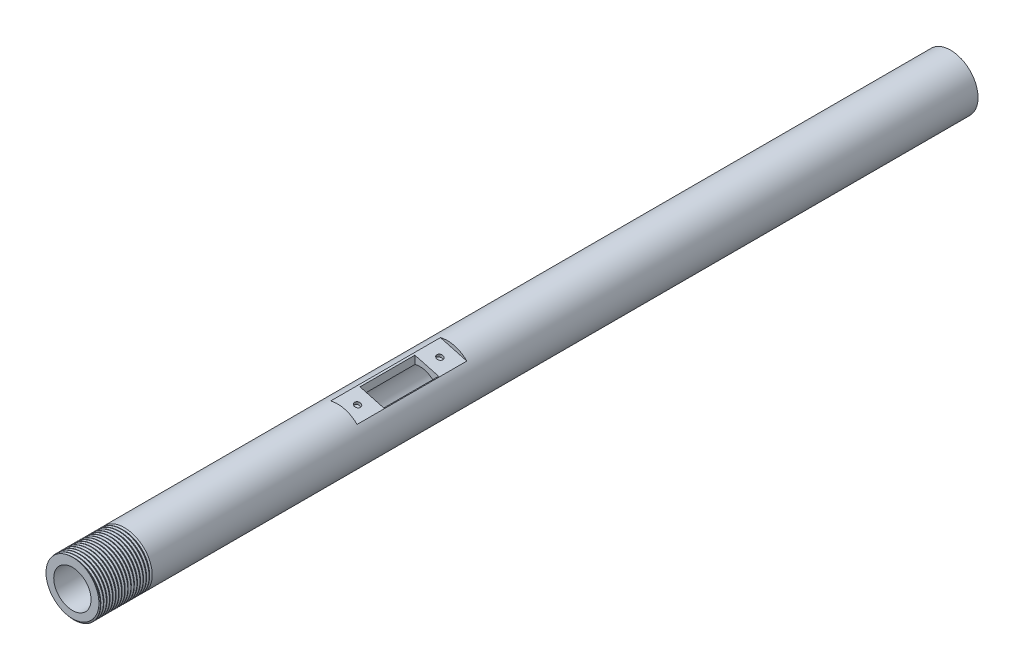
SolidWorks part; units mm, degrees
ref_plane "Front" through (0, 0, 0) normal (0, 0, 1) x (1, 0, 0)
ref_plane "Top" through (0, 0, 0) normal (0, 1, 0) x (1, 0, 0)
ref_plane "Right" through (0, 0, 0) normal (1, 0, 0) x (0, 0, -1)
sketch "Sketch2" plane through (0, 0, 0) normal (0, 0, 1) x (1, 0, 0)
  circle A0 centre (0, 0) radius 12.954
  circle A1 centre (0, 0) radius 19.05
  dimension "D1" = 38.1
  dimension "D2" = 25.908
extrude "Boss-Extrude1" add sketch "Sketch2" along normal blind 685.8
sketch "Sketch4" plane through (0, 0, 0) normal (0, 1, 0) x (1, 0, 0)
  line L0 (0, -685.8) -> (0, -403.662) construction
  line L1 (-19.05, -685.8) -> (19.05, -685.8) construction
  line L2 (12.954, -444.5) -> (12.954, -482.6)
  line L3 (12.954, -482.6) -> (-3.556, -482.6)
  line L4 (-3.556, -482.6) -> (-3.556, -444.5)
  line L5 (-3.556, -444.5) -> (12.954, -444.5)
  dimension "D1" = 12.954
  dimension "D2" = 16.51
  dimension "D3" = 38.1
  dimension "D4" = 203.2
extrude "Cut-Extrude2" cut sketch "Sketch4" along normal up to next
sketch "Sketch6" plane through (0, 0, 0) normal (0, 0, -1) x (-1, 0, 0)
  circle A1 centre (0, 0) radius 19.05
  circle A2 centre (0, 0) radius 19.05
  dimension "D1" = 0
ref_plane "Plane1" through (4.9305, 18.4009, 0) normal (0.2588, 0.9659, 0) x (0, 0, -1)
sketch "Sketch7" plane through (4.9305, 18.4009, 0) normal (0.2588, 0.9659, 0) x (0, 0, -1)
  line L0 (-482.6, -8.8975) -> (-482.6, 8.2787) construction
  line L1 (-425.45, -38.4094) -> (-501.65, -38.4094)
  line L2 (-425.45, -38.4094) -> (-425.45, 37.7906)
  line L3 (-425.45, 37.7906) -> (-501.65, 37.7906)
  line L4 (-501.65, -38.4094) -> (-501.65, 37.7906)
  line L5 (-425.45, -38.4094) -> (-501.65, 37.7906) construction
  line L6 (-425.45, 37.7906) -> (-501.65, -38.4094) construction
  line L7 (-482.6, -8.8975) -> (-482.6, 8.2787) construction
  line L8 (-444.5, 8.2787) -> (-444.5, -8.8975) construction
  line L9 (-444.5, 8.2787) -> (-444.5, -8.8975) construction
  line L10 (-482.6, -0.3094) -> (-501.65, -0.3094) construction
  line L11 (-444.5, -0.3094) -> (-425.45, -0.3094) construction
  point P4 (-463.55, -0.3094)
  dimension "D1" = 76.2
  dimension "D2" = 76.2
extrude "Cut-Extrude3" cut sketch "Sketch7" against normal blind 2.54
sketch "Sketch8" plane through (4.2731, 15.9474, 0) normal (0.2588, 0.9659, 0) x (0.9659, -0.2588, 0)
  line L0 (0, -425.45) -> (0, -444.5) construction
  line L1 (9.5038, -425.45) -> (-9.5038, -425.45) construction
  line L2 (8.9871, -444.5) -> (-8.1053, -444.5) construction
  line L3 (-9.5038, -463.55) -> (9.5038, -463.55) construction
  line L6 (-9.5038, -425.45) -> (-9.5038, -501.65) construction
  line L7 (9.5038, -501.65) -> (9.5038, -425.45) construction
  line L8 (0, -501.65) -> (0, -482.6) construction
  circle A0 centre (0, -434.975) radius 0.806
  circle A2 centre (0, -492.125) radius 0.806
hole_wizard "Tap Drill for M5x0.8 Tap1" positions "3DSketch1" profile "Sketch9" hole size "M5x0.8" standard "ANSI Metric"
sketch3d "3DSketch1"
  point P3 (4.2731, 15.9474, 434.975)
  point P7 (4.2731, 15.9474, 492.125)
sketch "Sketch9" plane through (4.2731, 15.9474, 434.975) normal (0, 0, 1) x (-0.9659, 0.2588, 0)
  line L0 (0, 0) -> (0, 3.2938)
  line L1 (0, 3.2938) -> (2.1, 2.032)
  line L2 (2.1, 2.032) -> (2.1, 0)
  line L5 (2.1, 0) -> (0, 0)
  line L10 (0, 3.2938) -> (-2.1, 2.032) construction
  line L11 (0, -6.35) -> (0, 107.95) construction
  dimension "Hole Dia." = 4.2
  dimension "Hole Depth" = 2.032
  dimension "Drill Angle" = 118
ref_plane "Plane3" through (0, 19.05, 0) normal (0, 1, 0) x (1, 0, 0)
extrude "Cut-Extrude4" cut sketch "Sketch6" against normal blind 76.2
thread "Thread1" pitch 2.1167 method cut profile "Thread Profile2" start angle 0, offset 2.54, length 38.1, pitch 2.1167, diameter 38.1
ref_plane "Plane5" through (-19.05, 0, 688.34) normal (0, -1, 0) x (-1, 0, 0)
sketch "Thread Profile2" plane through (-19.05, 0, 688.34) normal (0, -1, 0) x (-1, 0, 0)
  line L0 (0, 0) -> (0, 2.1167) construction
  line L11 (0, 0) -> (0, 1.8521)
  line L12 (0, 1.8521) -> (-1.1457, 1.1906)
  line L13 (-1.1457, 1.1906) -> (-1.1457, 0.6615)
  line L15 (-1.1457, 0.6615) -> (0, 0)
  line L17 (-1.1457, 0.926) -> (0, 0.926) construction
  point P2 (0, 0)
  dimension "Pitch" = 2.1167
  dimension "Profile_Angle" = 60
  dimension "Profile_Land" = 0.5292
  dimension "Profile_Height" = 1.1457
